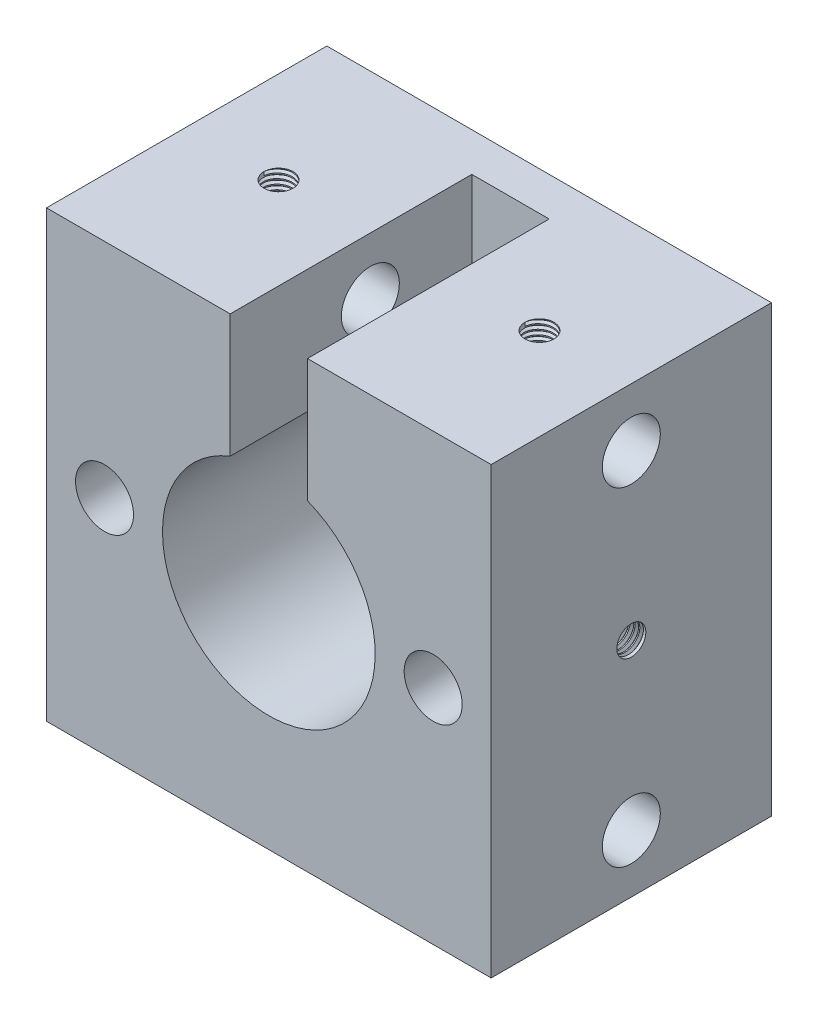
SolidWorks part; units mm, degrees
material "1060 Alloy"
ref_plane "Front Plane" through (0, 0, 0) normal (0, 0, 1) x (1, 0, 0)
ref_plane "Top Plane" through (0, 0, 0) normal (0, 1, 0) x (1, 0, 0)
ref_plane "Right Plane" through (0, 0, 0) normal (1, 0, 0) x (0, 0, -1)
sketch "Sketch1" plane through (0, 0, 0) normal (0, 0, 1) x (1, 0, 0)
  line L0 (0, 11) -> (0, 23) construction
  line L1 (-23, -23) -> (23, -23)
  line L2 (-23, -23) -> (-23, 23)
  line L3 (-23, 23) -> (23, 23)
  line L4 (23, -23) -> (23, 23)
  line L5 (-23, -23) -> (23, 23) construction
  line L6 (-23, 23) -> (23, -23) construction
  line L7 (0, -11) -> (0, -23) construction
  line L8 (-11, 0) -> (-23, 0) construction
  line L9 (11, 0) -> (23, 0) construction
  circle A0 centre (0, 0) radius 11
  dimension "D1" = 22
  dimension "D2" = 12
  dimension "D3" = 12
extrude "Boss-Extrude1" add sketch "Sketch1" along normal blind 25
sketch "Sketch4" plane through (0, 0, 0) normal (0, 0, -1) x (-1, 0, 0)
  line L1 (-23, -23) -> (23, -23)
  line L2 (-23, -23) -> (-23, 23)
  line L3 (-23, 23) -> (23, 23)
  line L4 (23, -23) -> (23, 23)
  line L5 (-23, -23) -> (23, 23) construction
  line L6 (-23, 23) -> (23, -23) construction
  point P0 (0, 0)
extrude "Boss-Extrude2" add sketch "Sketch4" along normal blind 4
sketch "Sketch3" plane through (23, 0, 0) normal (1, 0, 0) x (0, 0, -1)
  line L0 (-10.5, 23) -> (-10.5, 11) construction
  line L1 (-25, 23) -> (4, 23) construction
  line L2 (-10.5, -23) -> (-10.5, -11) construction
  line L3 (-25, -23) -> (4, -23) construction
  line L4 (0, 11) -> (0, 23) construction
  line L5 (0, -11) -> (0, -23) construction
  circle A0 centre (-10.5, 17) radius 3
  circle A1 centre (-10.5, -17) radius 3
  dimension "D1" = 6
extrude "Cut-Extrude2" cut sketch "Sketch3" against normal through all
sketch "Sketch2" plane through (0, 0, 25) normal (0, 0, 1) x (1, 0, 0)
  line L0 (11, 0) -> (23, 0) construction
  line L1 (23, -23) -> (23, 23) construction
  line L2 (-11, 0) -> (-23, 0) construction
  line L3 (-23, 23) -> (-23, -23) construction
  circle A0 centre (0, 0) radius 11 construction
  circle A1 centre (17, 0) radius 3
  circle A2 centre (-17, 0) radius 3
  dimension "D1" = 6
extrude "Cut-Extrude1" cut sketch "Sketch2" against normal through all
sketch "Sketch5" plane through (0, 0, 25) normal (0, 0, 1) x (1, 0, 0)
  line L0 (0, 11) -> (0, 23) construction
  line L1 (23, 23) -> (-23, 23) construction
  line L3 (-4, 7.5156) -> (4, 7.5156)
  line L4 (-4, 7.5156) -> (-4, 26.4844)
  line L5 (-4, 26.4844) -> (4, 26.4844)
  line L6 (4, 7.5156) -> (4, 26.4844)
  line L7 (-4, 7.5156) -> (4, 26.4844) construction
  line L8 (-4, 26.4844) -> (4, 7.5156) construction
  circle A0 centre (0, 0) radius 11 construction
  circle A1 centre (0, 0) radius 11 construction
  point P8 (0, 17)
  dimension "D1" = 8
extrude "Cut-Extrude3" cut sketch "Sketch5" against normal up to surface (25 mm away) up to face at (11, 0, 0)
sketch "Sketch6" plane through (0, 0, 0) normal (0, 0, 1) x (1, 0, 0)
  circle A0 centre (0, 0) radius 6.25
  dimension "D1" = 12.5
extrude "Cut-Extrude4" cut sketch "Sketch6" against normal through all
sketch "Sketch7" plane through (0, 0, -4) normal (0, 0, -1) x (-1, 0, 0)
  line L0 (0, 0) -> (6.364, 6.364) construction
  circle A0 centre (0, 0) radius 9 construction
  circle A1 centre (6.364, 6.364) radius 1
  circle A2 centre (6.364, -6.364) radius 1
  circle A3 centre (-6.364, -6.364) radius 1
  circle A4 centre (-6.364, 6.364) radius 1
  point P14 (0, 0)
  dimension "D1" = 18
  dimension "D2" = 2
  dimension "D3" = 4
extrude "Cut-Extrude5" cut sketch "Sketch7" against normal through all
sketch "Sketch9" plane through (0, 23, 0) normal (0, 1, 0) x (1, 0, 0)
  line L0 (-23, -10.5) -> (-4, -10.5) construction
  line L1 (-23, -25) -> (-23, 4) construction
  line L2 (-4, -25) -> (-4, 0) construction
  line L3 (23, -10.5) -> (4, -10.5) construction
  line L4 (23, -25) -> (23, 4) construction
  line L5 (4, 0) -> (4, -25) construction
  circle A0 centre (13.5, -10.5) radius 1.5
  circle A1 centre (-13.5, -10.5) radius 1.5
  dimension "D1" = 3
extrude "Cut-Extrude6" cut sketch "Sketch9" against normal up to next
thread "Thread1" pitch 0.5 method cut profile "Thread Profile1" start angle 0, offset 0, length 5, pitch 0.5, diameter 3
ref_plane "Plane1" through (12, 23, 10.5) normal (0, 0, 1) x (-1, 0, 0)
sketch "Thread Profile1" plane through (12, 23, 10.5) normal (0, 0, 1) x (-1, 0, 0)
  line L0 (0, 0) -> (0, 0.5) construction
  line L1 (0, 0) -> (0.2706, 0.1562)
  line L2 (0.2706, 0.1562) -> (0.2706, 0.2187)
  line L3 (0.2706, 0.2187) -> (0, 0.375)
  line L4 (0.2706, 0.1875) -> (0, 0.1875) construction
  line L11 (0, 0) -> (0, 0.375)
  point P2 (0, 0)
  dimension "Pitch" = 0.5
  dimension "Profile_Angle" = 60
  dimension "Profile_Land" = 0.0625
  dimension "Profile_Height" = 0.2706
thread "Thread2" pitch 0.5 method cut profile "Thread Profile2" start angle 0, offset 0, length 5, pitch 0.5, diameter 3
ref_plane "Plane2" through (-15, 23, 10.5) normal (0, 0, 1) x (-1, 0, 0)
sketch "Thread Profile2" plane through (-15, 23, 10.5) normal (0, 0, 1) x (-1, 0, 0)
  line L0 (0, 0) -> (0, 0.5) construction
  line L1 (0, 0) -> (0.2706, 0.1562)
  line L2 (0.2706, 0.1562) -> (0.2706, 0.2187)
  line L3 (0.2706, 0.2187) -> (0, 0.375)
  line L4 (0.2706, 0.1875) -> (0, 0.1875) construction
  line L11 (0, 0) -> (0, 0.375)
  point P2 (0, 0)
  dimension "Pitch" = 0.5
  dimension "Profile_Angle" = 60
  dimension "Profile_Land" = 0.0625
  dimension "Profile_Height" = 0.2706
sketch "Sketch15" plane through (0, -23, 0) normal (0, -1, 0) x (1, 0, 0)
  circle A0 centre (13.5, 10.5) radius 1.5 construction
  circle A1 centre (-13.5, 10.5) radius 1.5 construction
  circle A2 centre (13.5, 10.5) radius 1.5
  circle A3 centre (-13.5, 10.5) radius 1.5
extrude "Cut-Extrude7" cut sketch "Sketch15" against normal up to next
thread "Thread3" pitch 0.5 method cut profile "Thread Profile3" start angle 0, offset 0, length 5, pitch 0.5, diameter 3
ref_plane "Plane3" through (15, -23, 10.5) normal (0, 0, 1) x (1, 0, 0)
sketch "Thread Profile3" plane through (15, -23, 10.5) normal (0, 0, 1) x (1, 0, 0)
  line L0 (0, 0) -> (0, 0.5) construction
  line L1 (0, 0) -> (0.2706, 0.1562)
  line L2 (0.2706, 0.1562) -> (0.2706, 0.2187)
  line L3 (0.2706, 0.2187) -> (0, 0.375)
  line L4 (0.2706, 0.1875) -> (0, 0.1875) construction
  line L11 (0, 0) -> (0, 0.375)
  point P2 (0, 0)
  dimension "Pitch" = 0.5
  dimension "Profile_Angle" = 60
  dimension "Profile_Land" = 0.0625
  dimension "Profile_Height" = 0.2706
thread "Thread4" pitch 0.5 method cut profile "Thread Profile4" start angle 0, offset 0, length 5, pitch 0.5, diameter 3
ref_plane "Plane4" through (-12, -23, 10.5) normal (0, 0, 1) x (1, 0, 0)
sketch "Thread Profile4" plane through (-12, -23, 10.5) normal (0, 0, 1) x (1, 0, 0)
  line L0 (0, 0) -> (0, 0.5) construction
  line L1 (0, 0) -> (0.2706, 0.1562)
  line L2 (0.2706, 0.1562) -> (0.2706, 0.2187)
  line L3 (0.2706, 0.2187) -> (0, 0.375)
  line L4 (0.2706, 0.1875) -> (0, 0.1875) construction
  line L11 (0, 0) -> (0, 0.375)
  point P2 (0, 0)
  dimension "Pitch" = 0.5
  dimension "Profile_Angle" = 60
  dimension "Profile_Land" = 0.0625
  dimension "Profile_Height" = 0.2706
sketch "Sketch20" plane through (23, 0, 0) normal (1, 0, 0) x (0, 0, -1)
  line L0 (-10.5, 23) -> (-10.5, -23) construction
  line L1 (-25, 23) -> (4, 23) construction
  line L2 (-25, -23) -> (4, -23) construction
  circle A0 centre (-10.5, 0) radius 1.5
  dimension "D1" = 3
extrude "Cut-Extrude8" cut sketch "Sketch20" against normal up to next
thread "Thread5" pitch 0.5 method cut profile "Thread Profile5" start angle 0, offset 0, length 5, pitch 0.5, diameter 3
ref_plane "Plane5" through (23, 0, 12) normal (0, -1, 0) x (0, 0, 1)
sketch "Thread Profile5" plane through (23, 0, 12) normal (0, -1, 0) x (0, 0, 1)
  line L0 (0, 0) -> (0, 0.5) construction
  line L1 (0, 0) -> (0.2706, 0.1562)
  line L2 (0.2706, 0.1562) -> (0.2706, 0.2187)
  line L3 (0.2706, 0.2187) -> (0, 0.375)
  line L4 (0.2706, 0.1875) -> (0, 0.1875) construction
  line L11 (0, 0) -> (0, 0.375)
  point P2 (0, 0)
  dimension "Pitch" = 0.5
  dimension "Profile_Angle" = 60
  dimension "Profile_Land" = 0.0625
  dimension "Profile_Height" = 0.2706
sketch "Sketch23" plane through (-23, 0, 0) normal (-1, 0, 0) x (0, 0, 1)
  circle A0 centre (10.5, 0) radius 1.5 construction
  circle A1 centre (10.5, 0) radius 1.5
extrude "Cut-Extrude9" cut sketch "Sketch23" against normal up to next
thread "Thread6" pitch 0.5 method cut profile "Thread Profile6" start angle 0, offset 0, length 5, pitch 0.5, diameter 3
ref_plane "Plane6" through (-23, 0, 9) normal (0, -1, 0) x (0, 0, -1)
sketch "Thread Profile6" plane through (-23, 0, 9) normal (0, -1, 0) x (0, 0, -1)
  line L0 (0, 0) -> (0, 0.5) construction
  line L1 (0, 0) -> (0.2706, 0.1562)
  line L2 (0.2706, 0.1562) -> (0.2706, 0.2187)
  line L3 (0.2706, 0.2187) -> (0, 0.375)
  line L4 (0.2706, 0.1875) -> (0, 0.1875) construction
  line L11 (0, 0) -> (0, 0.375)
  point P2 (0, 0)
  dimension "Pitch" = 0.5
  dimension "Profile_Angle" = 60
  dimension "Profile_Land" = 0.0625
  dimension "Profile_Height" = 0.2706
